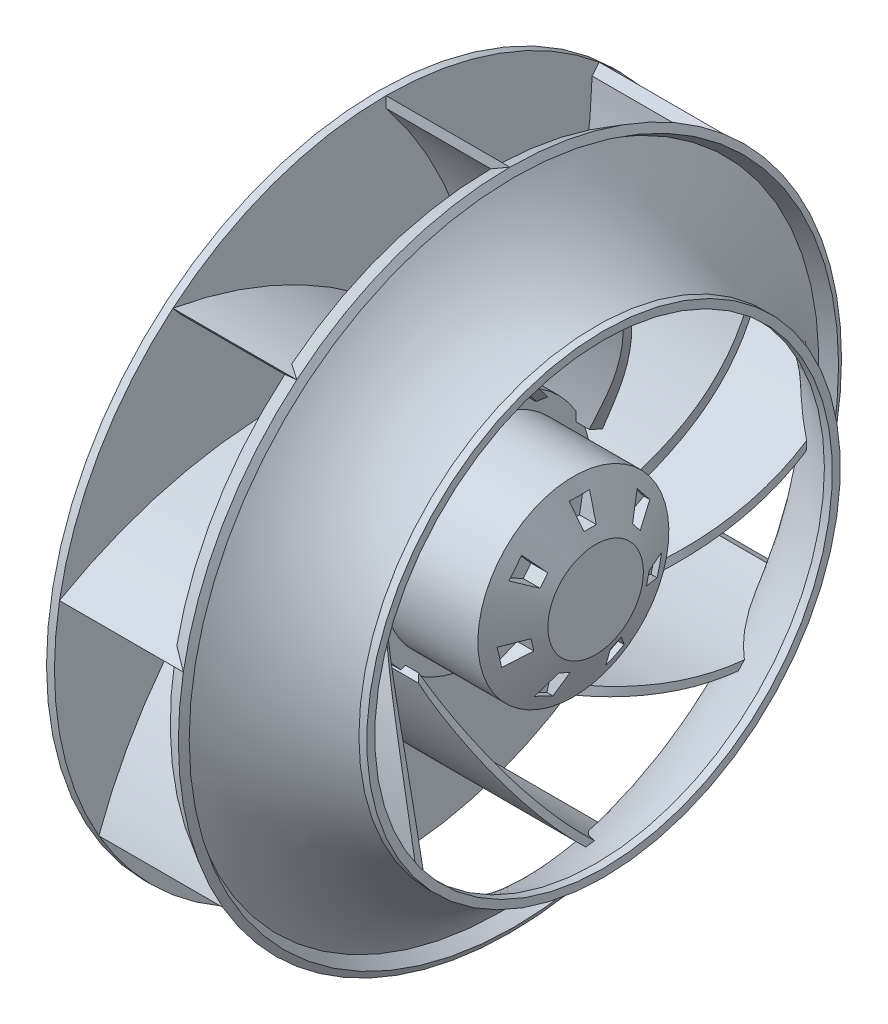
SolidWorks part; units mm, degrees
ref_plane "Front" through (0, 0, 0) normal (0, 0, 1) x (1, 0, 0)
ref_plane "Top" through (0, 0, 0) normal (0, 1, 0) x (1, 0, 0)
ref_plane "Right" through (0, 0, 0) normal (1, 0, 0) x (0, 0, -1)
sketch "Support-Front" plane through (0, 0, 0) normal (0, 0, 1) x (1, 0, 0)
  line L0 (0, 0) -> (0, 125)
  line L1 (0, 125) -> (3, 125)
  line L2 (3, 125) -> (3, 0)
  line L3 (3, 0) -> (0, 0) construction
  line L4 (3, 36) -> (73.6065, 36)
  line L5 (82, 18) -> (73.6065, 36)
  line L6 (82, 18) -> (82, 0)
  line L7 (0, 50.5) -> (-3, 48.7679)
  line L8 (-3, 48.7679) -> (-9, 48.7679)
  line L9 (-9, 48.7679) -> (-9, 0)
  line L10 (-9, 37.5) -> (-14, 37.5)
  line L11 (-14, 37.5) -> (-14, 0)
  line L12 (-14, 0) -> (0, 0) construction
  line L13 (3, 0) -> (82, 0) construction
  line L14 (51.1908, 122.4019) -> (46.4438, 119.6612)
  line L15 (82, 89.25) -> (85, 89.25)
  line L16 (85, 89.25) -> (85, 86.25)
  line L17 (85, 86.25) -> (82, 86.25)
  line L18 (49.6908, 125) -> (42.5, 120.8484)
  line L19 (49.6908, 125) -> (51.1908, 122.4019)
  line L20 (3, 125) -> (49.6908, 125) construction
  line L21 (82, 89.25) -> (82, 18) construction
  line L22 (82, 89.25) -> (82, 120.8484) construction
  line L23 (82, 120.8484) -> (42.5, 120.8484) construction
  line L24 (3, 125) -> (42.5, 120.8484) construction
  line L25 (42.5, 120.8484) -> (3, 120.8484) construction
  line L26 (82, 86.25) -> (0, 86.25) construction
  line L27 (-3, 48.7679) -> (0, 48.7679) construction
  line L28 (38.3032, 36) -> (38.3032, 86.25) construction
  line L29 (38.3032, 86.25) -> (38.3032, 120.8484) construction
  line L30 (38.3032, 36) -> (38.3032, 18) construction
  line L31 (38.3032, 18) -> (38.3032, 0) construction
  line L32 (49.6908, 125) -> (82, 125) construction
  line L33 (82, 125) -> (82, 89.25) construction
  line L34 (3, 57.2539) -> (82, 57.2539) construction
  line L35 (38.3032, 36) -> (82, 36) construction
  line L36 (82, 36) -> (82, 86.25) construction
  line L37 (82, 125) -> (67.5453, 94.0017) construction
  line L38 (3, 120.8484) -> (0, 120.8484) construction
  line L39 (38.3032, 36) -> (38.3032, 42.2249)
  line L40 (38.3032, 42.2249) -> (3, 42.2249)
  line L41 (3, 36) -> (38.3032, 42.2249) construction
  line L42 (0, 18) -> (82, 18) construction
  line L43 (82, 18) -> (0, 22.2974) construction
  line L44 (-3, 48.7679) -> (-3, 0) construction
  line L45 (0, 57.2539) -> (3, 57.2539)
  line L46 (0, 50.5) -> (3, 50.5)
  line L47 (1, 48.7679) -> (1, 0) construction
  line L48 (0, 50.5) -> (38.3032, 57.2539) construction
  arc A1 (46.4438, 119.6612) -> (82, 89.25) centre (113.1108, 161.6156) ccw
  arc A2 (42.5, 120.8484) -> (82, 86.25) centre (113.1108, 161.6156) ccw
  arc A3 (67.5453, 94.0017) -> (38.3032, 36) centre (-13.8554, 98.6684) cw
  point P37 (38.3032, 57.2539)
  dimension "Diam-Contact" = 75
  dimension "D2" = 3
  dimension "D3" = 10
  dimension "Diam-Total" = 250
  dimension "D5" = 150
  dimension "Width-Contact" = 5
  dimension "Width-Total" = 99
  dimension "Diam-Out" = 172.5
  dimension "D8" = 25
  dimension "Thickness" = 3
  dimension "Width-Out" = 85
  dimension "D11" = 30
  dimension "D12" = 6
  dimension "D13" = 25
  dimension "D14" = 10
  dimension "D15" = 3
  dimension "Depth-Hole" = 6
  dimension "Diam-Motor" = 101
  dimension "Diam-Motor-Inner" = 72
  dimension "Depth-Hole-Outer" = 10
sketch "Support-Right-Blade" plane through (0, 0, 0) normal (1, 0, 0) x (0, 0, -1)
  line L0 (38.9448, 18) -> (0, 18) construction
  line L1 (0, 125) -> (0, 120.8484)
  line L2 (0, 0) -> (0, 125) construction
  line L3 (38.9448, 18) -> (36.3071, 18)
  line L4 (0, 125) -> (38.9448, 18) construction
  line L5 (0, 125) -> (0, 18) construction
  arc A0 (0, 125) -> (38.9448, 18) centre (-127.5176, 18) cw
  arc A1 (36.3071, 18) -> (0, 120.8484) centre (-127.5176, 18) ccw
  dimension "D1" = 20
sketch "Support-Right" plane through (0, 0, 0) normal (1, 0, 0) x (0, 0, -1)
  line L1 (0, 0) -> (0, 36) construction
  line L2 (-2.3139, 22.2974) -> (2.3139, 22.2974)
  line L3 (2.3139, 22.2974) -> (3.8365, 30.9329)
  line L4 (3.8365, 30.9329) -> (-3.8365, 30.9329)
  line L5 (-3.8365, 30.9329) -> (-2.3139, 22.2974)
  line L6 (-2.3139, 22.2974) -> (-2.3139, 30.9329) construction
  line L7 (-2.3139, 30.9329) -> (0, 22.2974) construction
  circle A0 centre (0, 0) radius 36 construction
  circle A2 centre (0, 0) radius 31.1699 construction
  circle A3 centre (0, 0) radius 22.2974 construction
  point P10 (0, 22.2974)
  point P11 (0, 30.9329)
  dimension "D1" = 62.3397
  dimension "D2" = 15
  dimension "D3" = 10
sketch "Support-Right-Contact" plane through (0, 0, 0) normal (1, 0, 0) x (0, 0, -1)
  line L0 (0, 36) -> (0, -36)
  line L1 (-25.4558, 25.4558) -> (25.4558, -25.4558)
  line L2 (25.4558, 25.4558) -> (-25.4558, -25.4558)
  line L3 (36, 0) -> (-36, 0)
  line L4 (0, 0) -> (0, 18) construction
  line L5 (0, 18) -> (0, 36) construction
  line L6 (25.4558, -25.4558) -> (22.0404, -22.0404) construction
  line L7 (22.0404, -22.0404) -> (19.9191, -24.1617) construction
  line L8 (20.5915, -22.4287) -> (20.3073, -22.7129)
  line L9 (22.0404, -22.0404) -> (20.9798, -20.9798) construction
  line L10 (21.5101, -21.5101) -> (20.5915, -22.4287) construction
  line L11 (21.6522, -23.4893) -> (21.368, -23.7735)
  line L12 (0, 0) -> (19.9191, -24.1617) construction
  circle A0 centre (0, 0) radius 36
  circle A1 centre (0, 0) radius 27
  circle A2 centre (22.0404, -22.0404) radius 1.5
  circle A3 centre (0, 0) radius 31.1699 construction
  circle A4 centre (19.9191, -24.1617) radius 1.5
  point P15 (0, 27)
  dimension "Diam-Cable" = 3
  dimension "D1" = 45
  dimension "D2" = 45
  dimension "D3" = 45
  dimension "D4" = 90
  dimension "Start-Angle-Fixing-Hole" = 360
sketch "Support-Right-Hole" plane through (0, 0, 0) normal (1, 0, 0) x (0, 0, -1)
  line L0 (0, 36) -> (0, 29) construction
  line L1 (0, 36) -> (0, -36) construction
  line L2 (0, 29) -> (0, 45) construction
  circle A0 centre (0, 0) radius 29 construction
  circle A1 centre (0, 29) radius 2
  circle A2 centre (0, 45) radius 3
  circle A3 centre (0, 0) radius 45 construction
  dimension "CC-Fixing-hole" = 58
  dimension "Diam-Fixing-Hole" = 4
  dimension "Diam-Fixing-Hole-Outer" = 6
  dimension "CC-Fixing-Hole-Outer" = 90
ref_plane "Plane1" through (82, 0, 0) normal (1, 0, 0) x (0, 0, -1)
ref_plane "Plane2" through (73.6065, 0, 0) normal (1, 0, 0) x (0, 0, -1)
ref_plane "Plane3" through (-9, 0, 0) normal (1, 0, 0) x (0, 0, -1)
ref_plane "Plane4" through (-3, 0, 0) normal (1, 0, 0) x (0, 0, -1)
ref_plane "Plane5" through (0, 0, 0) normal (0, 0.7071, -0.7071) x (1, 0, 0)
ref_plane "Plane6" through (-14, 0, 0) normal (1, 0, 0) x (0, 0, -1)
ref_plane "Plane7" through (1, 0, 0) normal (1, 0, 0) x (0, 0, -1)
sketch "Sketch4" plane through (0, 0, 0) normal (0, 0, 1) x (1, 0, 0)
  line L0 (3, 0) -> (0, 0) construction
  line L1 (3, 125) -> (3, 0) construction
  line L2 (0, 125) -> (3, 125) construction
  line L3 (0, 0) -> (0, 125) construction
  line L4 (3, 0) -> (0, 0) construction
  line L5 (3, 125) -> (3, 0)
  line L6 (0, 125) -> (3, 125)
  line L7 (0, 0) -> (0, 125)
  line L8 (3, 0) -> (0, 0)
revolve "Body-Plate" add sketch "Sketch4" angle 360 about L4
sketch "Sketch5" plane through (0, 0, 0) normal (0, 0, 1) x (1, 0, 0)
  line L0 (3, 0) -> (82, 0) construction
  line L1 (82, 18) -> (82, 0) construction
  line L2 (82, 18) -> (73.6065, 36) construction
  line L3 (3, 125) -> (3, 0) construction
  line L4 (3, 36) -> (73.6065, 36) construction
  line L5 (3, 0) -> (82, 0) construction
  line L6 (82, 18) -> (82, 0)
  line L7 (82, 18) -> (73.6065, 36)
  line L8 (3, 42.2249) -> (3, 0)
  line L9 (38.3032, 36) -> (73.6065, 36)
  line L10 (3, 0) -> (82, 0)
  line L11 (38.3032, 42.2249) -> (3, 42.2249) construction
  line L12 (38.3032, 36) -> (38.3032, 42.2249) construction
  line L13 (38.3032, 42.2249) -> (3, 42.2249)
  line L14 (38.3032, 36) -> (38.3032, 42.2249)
revolve "Body-Inner" add sketch "Sketch5" angle 360 about L5
sketch "Sketch6" plane through (0, 0, 0) normal (0, 0, 1) x (1, 0, 0)
  line L0 (-14, 0) -> (0, 0) construction
  line L1 (-9, 48.7679) -> (-9, 0) construction
  line L2 (-3, 48.7679) -> (-9, 48.7679) construction
  line L3 (0, 50.5) -> (-3, 48.7679) construction
  line L4 (0, 0) -> (0, 125) construction
  line L5 (-14, 0) -> (0, 0) construction
  line L6 (-9, 48.7679) -> (-9, 0)
  line L7 (-3, 48.7679) -> (-9, 48.7679)
  line L8 (0, 50.5) -> (-3, 48.7679)
  line L9 (0, 0) -> (0, 50.5)
  line L10 (0, 0) -> (-9, 0)
revolve "Body-Motor" add sketch "Sketch6" angle 360 about L5
sketch "Sketch7" plane through (0, 0, 0) normal (0, 0, 1) x (1, 0, 0)
  line L0 (-14, 0) -> (0, 0) construction
  line L1 (-14, 37.5) -> (-14, 0) construction
  line L2 (-9, 48.7679) -> (-9, 0) construction
  line L3 (-9, 37.5) -> (-14, 37.5) construction
  line L4 (-14, 0) -> (0, 0) construction
  line L5 (-14, 37.5) -> (-14, 0)
  line L6 (-9, 37.5) -> (-9, 0)
  line L7 (-9, 37.5) -> (-14, 37.5)
  line L8 (-14, 0) -> (-9, 0)
revolve "Contact" add sketch "Sketch7" angle 360 about L4
sketch "Sketch9" plane through (0, 0, 0) normal (1, 0, 0) x (0, 0, -1)
  line L0 (0, 125) -> (0, 120.8484) construction
  line L1 (38.9448, 18) -> (36.3071, 18) construction
  line L2 (0, 125) -> (0, 120.8484)
  line L3 (38.9448, 18) -> (36.3071, 18)
  arc A0 (38.9448, 18) -> (0, 125) centre (-127.5176, 18) ccw construction
  arc A1 (36.3071, 18) -> (0, 120.8484) centre (-127.5176, 18) ccw construction
  arc A2 (38.9448, 18) -> (0, 125) centre (-127.5176, 18) ccw
  arc A3 (36.3071, 18) -> (0, 120.8484) centre (-127.5176, 18) ccw
extrude "Blade" add sketch "Sketch9" along normal up to surface (82 mm away) up to plane "Plane1"
pattern_circular "Pattern-Blade" count 9 over 360 about axis through (3, 0, 0) along (1, 0, 0) of "Blade"
sketch "Sketch8" plane through (0, 0, 0) normal (0, 0, 1) x (1, 0, 0)
  line L0 (3, 0) -> (82, 0) construction
  line L1 (3, 0) -> (82, 0) construction
  line L6 (49.6908, 125) -> (42.5, 120.8484)
  line L7 (51.1908, 122.4019) -> (49.6908, 125)
  line L8 (46.4438, 119.6612) -> (51.1908, 122.4019)
  line L9 (85, 89.25) -> (82, 89.25)
  line L10 (85, 86.25) -> (85, 89.25)
  line L11 (82, 86.25) -> (85, 86.25)
  line L12 (49.6908, 125) -> (42.5, 120.8484)
  line L13 (51.1908, 122.4019) -> (49.6908, 125)
  line L14 (46.4438, 119.6612) -> (51.1908, 122.4019)
  line L15 (85, 89.25) -> (82, 89.25)
  line L16 (85, 86.25) -> (85, 89.25)
  line L17 (82, 86.25) -> (85, 86.25)
  arc A2 (46.4438, 119.6612) -> (82, 89.25) centre (113.1108, 161.6156) ccw
  arc A3 (42.5, 120.8484) -> (82, 86.25) centre (113.1108, 161.6156) ccw
  arc A4 (46.4438, 119.6612) -> (82, 89.25) centre (113.1108, 161.6156) ccw
  arc A5 (42.5, 120.8484) -> (82, 86.25) centre (113.1108, 161.6156) ccw
  dimension "D1" = 0
revolve "Body-Outer" add sketch "Sketch8" angle 360 about L1
sketch "Sketch11" plane through (0, 0, 0) normal (0, 0, 1) x (1, 0, 0)
  line L0 (82, 89.25) -> (82, 120.8484) construction
  line L1 (82, 18) -> (73.6065, 36) construction
  line L2 (49.6908, 125) -> (82, 125) construction
  line L3 (82, 89.25) -> (82, 125)
  line L4 (49.6908, 125) -> (51.1908, 122.4019) construction
  line L5 (49.6908, 125) -> (82, 125)
  line L6 (3, 0) -> (82, 0) construction
  line L7 (3, 0) -> (82, 0) construction
  line L8 (51.1908, 122.4019) -> (46.4438, 119.6612) construction
  line L9 (49.6908, 125) -> (51.1908, 122.4019)
  line L10 (51.1908, 122.4019) -> (46.4438, 119.6612)
  line L11 (82, 89.25) -> (82, 18) construction
  line L12 (38.3032, 36) -> (82, 36) construction
  line L13 (82, 86.25) -> (82, 18)
  line L14 (38.3032, 36) -> (73.6065, 36)
  line L15 (82, 18) -> (73.6065, 36)
  arc A0 (46.4438, 119.6612) -> (82, 89.25) centre (113.1108, 161.6156) ccw construction
  arc A1 (46.4438, 119.6612) -> (82, 89.25) centre (113.1108, 161.6156) ccw
  arc A2 (42.5, 120.8484) -> (82, 86.25) centre (113.1108, 161.6156) ccw construction
  arc A3 (38.3032, 36) -> (67.5453, 94.0017) centre (-13.8554, 98.6684) ccw construction
  arc A4 (67.5453, 94.0017) -> (82, 86.25) centre (113.1108, 161.6156) ccw
  arc A5 (38.3032, 36) -> (67.5453, 94.0017) centre (-13.8554, 98.6684) ccw
revolve "Cut-Blade" cut sketch "Sketch11" angle 360 about L7
sketch "Sketch13" plane through (73.6065, 0, 0) normal (1, 0, 0) x (0, 0, -1)
  line L0 (3.8365, 30.9329) -> (-3.8365, 30.9329) construction
  line L1 (-3.8365, 30.9329) -> (-2.3139, 22.2974) construction
  line L2 (2.3139, 22.2974) -> (3.8365, 30.9329) construction
  line L3 (-2.3139, 22.2974) -> (2.3139, 22.2974) construction
  line L4 (3.8365, 30.9329) -> (-3.8365, 30.9329)
  line L5 (-3.8365, 30.9329) -> (-2.3139, 22.2974)
  line L6 (2.3139, 22.2974) -> (3.8365, 30.9329)
  line L7 (-2.3139, 22.2974) -> (2.3139, 22.2974)
extrude "Cut-Body-Inner" cut sketch "Sketch13" along normal through all
pattern_circular "Pattern-Cut-Body-Inner" count 7 over 360 about axis through (3, 0, 0) along (1, 0, 0) of "Cut-Body-Inner"
sketch "Sketch16" plane through (-9, 0, 0) normal (1, 0, 0) x (0, 0, -1)
  line L0 (25.4558, 25.4558) -> (-25.4558, -25.4558) construction
  line L1 (0, 36) -> (0, -36) construction
  line L2 (-25.4558, 25.4558) -> (25.4558, -25.4558) construction
  line L3 (25.4558, 25.4558) -> (19.0919, 19.0919)
  line L4 (0, 36) -> (0, 27)
  line L5 (-25.4558, 25.4558) -> (-19.0919, 19.0919)
  line L6 (36, 0) -> (-36, 0) construction
  line L7 (36, 0) -> (27, 0)
  line L8 (-27, 0) -> (-36, 0)
  line L9 (19.0919, -19.0919) -> (25.4558, -25.4558)
  line L10 (0, -27) -> (0, -36)
  line L11 (-19.0919, -19.0919) -> (-25.4558, -25.4558)
  circle A0 centre (0, 0) radius 27 construction
  circle A1 centre (0, 0) radius 36 construction
  arc A2 (19.0919, 19.0919) -> (0, 27) centre (0, 0) ccw
  arc A3 (0, 36) -> (-25.4558, 25.4558) centre (0, 0) ccw
  arc A4 (36, 0) -> (25.4558, 25.4558) centre (0, 0) ccw
  arc A5 (19.0919, -19.0919) -> (27, 0) centre (0, 0) ccw
  arc A6 (0, -36) -> (25.4558, -25.4558) centre (0, 0) ccw
  arc A7 (-19.0919, -19.0919) -> (0, -27) centre (0, 0) ccw
  arc A8 (-36, 0) -> (-25.4558, -25.4558) centre (0, 0) ccw
  arc A9 (-19.0919, 19.0919) -> (-27, 0) centre (0, 0) ccw
extrude "Cut-Contact" [suppressed] cut sketch "Sketch16" against normal through all
sketch "Sketch17" plane through (-3, 0, 0) normal (1, 0, 0) x (0, 0, -1)
  circle A0 centre (0, 29) radius 2 construction
  circle A1 centre (0, 29) radius 2
extrude "Fixing-Hole" cut sketch "Sketch17" against normal through all
pattern_circular "Pattern-Fixing-Hole" count 4 over 360 about axis through (-14, 0, 0) along (1, 0, 0) of "Fixing-Hole"
sketch "Sketch22" plane through (1, 0, 0) normal (1, 0, 0) x (0, 0, -1)
  circle A0 centre (0, 45) radius 3 construction
  circle A1 centre (0, 45) radius 3
extrude "Fixing-Hole-Outer" cut sketch "Sketch22" against normal through all
sketch "Sketch20" plane through (-9, 0, 0) normal (1, 0, 0) x (0, 0, -1)
  circle A1 centre (22.0404, -22.0404) radius 1.5 construction
  circle A3 centre (22.0404, -22.0404) radius 1.5
sketch "Sketch19" plane through (0, 0, 0) normal (0, 0.7071, -0.7071) x (1, 0, 0)
  line L1 (-9, 31.1699) -> (0, 31.1699) construction
  line L2 (-14, 36.1699) -> (-14, 70.654)
  line L3 (-9, -34.4841) -> (-9, 0) construction
  line L4 (-14, -26.5165) -> (-14, 0) construction
  line L5 (-3, -34.4841) -> (-3, 0) construction
  arc A1 (-9, 31.1699) -> (-14, 36.1699) centre (-9, 36.1699) cw
pattern_circular "Pattern-Fixing-Hole-Outer" count 4 over 360 about axis through (3, 0, 0) along (1, 0, 0) of "Fixing-Hole-Outer"
sweep "Cable" [suppressed] add profiles "Sketch20" path "Sketch19"
sketch "Sketch23" plane through (-9, 0, 0) normal (1, 0, 0) x (0, 0, -1)
  line L0 (20.5915, -22.4287) -> (20.3073, -22.7129) construction
  line L1 (21.6522, -23.4893) -> (21.368, -23.7735) construction
  line L2 (20.5915, -22.4287) -> (20.3073, -22.7129)
  line L3 (21.6522, -23.4893) -> (21.368, -23.7735)
  circle A0 centre (19.9191, -24.1617) radius 1.5 construction
  arc A1 (20.3073, -22.7129) -> (21.368, -23.7735) centre (19.9191, -24.1617) ccw
  circle A2 centre (22.0404, -22.0404) radius 1.5 construction
  arc A3 (21.6522, -23.4893) -> (20.5915, -22.4287) centre (22.0404, -22.0404) ccw
sketch "Sketch25" [suppressed] plane through (0, 0, 0) normal (0, 0.7071, -0.7071) x (1, 0, 0)
  line L0 (0, 31.1699) -> (-9, 31.1699) construction
  line L1 (-14, 36.1699) -> (-14, 70.654) construction
  line L2 (-14, 36.1699) -> (-14, 70.654)
  line L3 (-12.5, 70.654) -> (-15.5, 70.654) construction
  arc A0 (-9, 31.1699) -> (-14, 36.1699) centre (-9, 36.1699) cw
sweep "Cable-2" [suppressed] add profiles "Sketch23" path "Sketch25"
sketch "Sketch21" plane through (0, 0, 0) normal (0, 0, 1) x (1, 0, 0)
  line L0 (0, 0) -> (0, 125) construction
  line L1 (3, 125) -> (3, 0) construction
  line L2 (0, 50.5) -> (3, 50.5) construction
  line L3 (0, 57.2539) -> (3, 57.2539) construction
  line L4 (0, 50.5) -> (0, 57.2539)
  line L5 (3, 57.2539) -> (3, 50.5)
  line L6 (0, 50.5) -> (3, 50.5)
  line L7 (0, 57.2539) -> (3, 57.2539)
  line L8 (-14, 0) -> (0, 0) construction
  line L9 (-14, 0) -> (0, 0) construction
revolve "Cut-Body" cut sketch "Sketch21" angle 360 about L9
scale "Scale1" bodies to scale 111 scale about centroid uniform scaling yes scale factor 1.24
sketch "Sketch28" plane through (0, 0, 0) normal (0, 1, 0) x (1, 0, 0)
  line L0 (-18.0426, 60.4723) -> (-18.0426, -60.4723) construction
  line L4 (-18.0426, 15) -> (-24.2426, 15)
  line L5 (-18.0426, 15) -> (-18.0426, -15)
  line L6 (-18.0426, -15) -> (-24.2426, -15)
  line L7 (-24.2426, 15) -> (-24.2426, -15)
  line L8 (-24.2426, 46.5) -> (-24.2426, -46.5) construction
  line L9 (54.734, 0) -> (-3.1626, 0) construction
  point P8 (-18.0426, 0)
  dimension "D1" = 30
extrude "Boss-Extrude1" add sketch "Sketch28" along normal blind 69
sketch "Sketch30" plane through (-24.2426, 0, 0) normal (-1, 0, 0) x (0, 0, 1)
  circle A0 centre (0, 0) radius 60.4723 construction
  circle A1 centre (0, 0) radius 60.4723
  circle A2 centre (0, 0) radius 71.4723
  dimension "D1" = 11
extrude "Cut-Extrude1" cut sketch "Sketch30" against normal blind 7
sketch "Sketch31" plane through (0, 0, 0) normal (0, 1, 0) x (1, 0, 0)
  line L0 (-24.2426, 0) -> (-10.6026, 0) construction
  line L1 (-24.2426, 15) -> (-24.2426, -15) construction
  line L2 (-10.6026, -60.4723) -> (-10.6026, 60.4723) construction
  circle A0 centre (-17.4226, 7.0221) radius 4.5
  circle A1 centre (-17.4226, -6.7571) radius 3
  dimension "D1" = 9
  dimension "D2" = 6
extrude "Boss-Extrude2" add sketch "Sketch31" along normal blind 69
sketch "Sketch32" plane through (0, 69, 0) normal (0, 1, 0) x (1, 0, 0)
  point P0 (-17.4226, 7.0221)
  point P1 (-17.4226, -6.7571)
other "CPoint1" parameters "Diameter"=3, "StubLength"=5
ref_axis "Axis1" through (-17.4226, 79, -7.0221) along (0, -1, 0)
other "CPoint2" parameters "Diameter"=3, "StubLength"=4.5
ref_axis "Axis4" through (-17.4226, 79, 6.7571) along (0, -1, 0)
